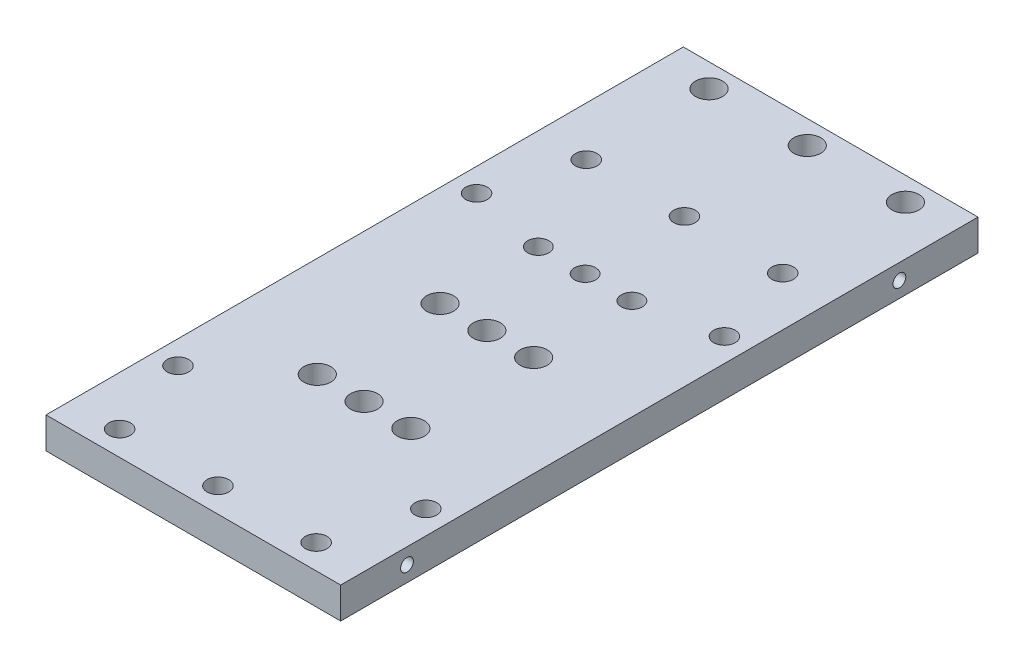
SolidWorks part; units mm, degrees
material "6061 Alloy"
ref_plane "Front Plane" through (0, 0, 0) normal (0, 0, 1) x (1, 0, 0)
ref_plane "Top Plane" through (0, 0, 0) normal (0, 1, 0) x (1, 0, 0)
ref_plane "Right Plane" through (0, 0, 0) normal (1, 0, 0) x (0, 0, -1)
sketch "Sketch1" plane through (0, 0, 0) normal (0, 1, 0) x (1, 0, 0)
  line L1 (-30, 80) -> (30, 80)
  line L2 (-30, 80) -> (-30, -80)
  line L3 (-30, -80) -> (30, -80)
  line L4 (30, 80) -> (30, -80)
  line L5 (0, -80) -> (0, 80) construction
  line L6 (-30, 0) -> (30, 0) construction
  point P0 (0, 0)
  dimension "D1" = 60
  dimension "D2" = 160
extrude "Boss-Extrude1" add sketch "Sketch1" along normal mid plane 6.35
sketch "Sketch3" plane through (0, 0, 0) normal (0, 1, 0) x (1, 0, 0)
  line L0 (0, 75.2375) -> (20, 75.2375) construction
  line L5 (0, -80) -> (0, 80) construction
  line L6 (-30, 0) -> (30, 0) construction
  line L7 (0, 50.2375) -> (20, 50.2375) construction
  line L8 (30, 80) -> (-30, 80) construction
  line L9 (-30, 80) -> (-30, -80) construction
  line L10 (-30, -80) -> (30, -80) construction
  line L11 (30, -80) -> (30, 80) construction
  line L12 (0, -44.7625) -> (20, -44.7625) construction
  circle A0 centre (20, 75.2375) radius 2.75
  circle A1 centre (20, 50.2375) radius 2.2
  circle A2 centre (-20, 50.2375) radius 2.2
  circle A3 centre (-20, 75.2375) radius 2.75
  circle A4 centre (0, 75.2375) radius 2.75
  circle A5 centre (0, 50.2375) radius 2.2
  circle A6 centre (20, -44.7625) radius 2.2
  circle A7 centre (-20, -44.7625) radius 2.2
  circle A8 centre (0, -44.7625) radius 2.2
  point P0 (0, 0)
  dimension "D4" = 5.5
  dimension "D5" = 4.4
  dimension "D1" = 4.7625
  dimension "D2" = 25
  dimension "D3" = 20
  dimension "D6" = 2
extrude "M4/5_through" cut sketch "Sketch3" against normal up to surface (3.175 mm away) and the other way blind 6.35 up to face at (0, -3.175, 0)
sketch "Sketch4" plane through (0, 0, -80) normal (0, 0, -1) x (-1, 0, 0)
  line L0 (0, 0) -> (-12, 0) construction
  line L1 (0, 0) -> (0, 3.175) construction
  line L2 (-30, 3.175) -> (30, 3.175) construction
  circle A0 centre (-12, 0) radius 1.3
  circle A1 centre (12, 0) radius 1.3
  dimension "D1" = 2.6
  dimension "D2" = 12
extrude "M3_DRILL" cut sketch "Sketch4" against normal blind 8
sketch "Sketch5" plane through (0, 3.175, 0) normal (0, 1, 0) x (1, 0, 0)
  line L0 (-20, -44.7625) -> (0, -44.7625) construction
  line L1 (-30, 80) -> (-30, -80) construction
  line L2 (0, 0) -> (0, -23.6676) construction
  line L3 (-20, 50.2375) -> (-20, -44.7625) construction
  line L4 (-20, 2.7375) -> (-9.1233, 2.7375) construction
  circle A0 centre (-25.2375, -27.6625) radius 2.2
  circle A1 centre (25.2375, -27.6625) radius 2.2
  circle A2 centre (25.2375, 33.1375) radius 2.2
  circle A3 centre (-25.2375, 33.1375) radius 2.2
  dimension "D2" = 4.4
  dimension "D1" = 17.1
  dimension "D3" = 4.7625
extrude "M4_through" cut sketch "Sketch5" against normal up to surface (6.35 mm away) up to face at (20, -3.175, -48.0375)
sketch "Sketch6" plane through (0, 3.175, 0) normal (0, 1, 0) x (1, 0, 0)
  line L0 (0, 0) -> (0, -64.4319) construction
  circle A0 centre (0, 30) radius 2.15
  circle A1 centre (9.53, 30) radius 2.15
  circle A2 centre (-9.53, 30) radius 2.15
  dimension "D1" = 4.3
  dimension "D4" = 30
  dimension "D2" = 2
  dimension "D3" = 2
extrude "M5_DRILL" cut sketch "Sketch6" against normal up to surface (6.35 mm away) up to face at (-25.2375, -3.175, -30.9375)
sketch "Sketch7" plane through (0, 3.175, 0) normal (0, 1, 0) x (1, 0, 0)
  line L0 (0, 30) -> (0, -15) construction
  circle A0 centre (0, 10) radius 2.75
  circle A1 centre (0, -15) radius 2.75
  circle A2 centre (9.53, 10) radius 2.75
  circle A3 centre (9.53, -15) radius 2.75
  circle A4 centre (-9.53, 10) radius 2.75
  circle A5 centre (-9.53, -15) radius 2.75
  dimension "D3" = 5.5
  dimension "D1" = 45
  dimension "D2" = 20
  dimension "D4" = 2
  dimension "D5" = 2
extrude "M5_through" cut sketch "Sketch7" against normal up to surface (6.35 mm away) up to face at (-9.53, -3.175, -27.85)
sketch "Sketch8" plane through (0, 3.175, 0) normal (0, 1, 0) x (1, 0, 0)
  line L0 (-20, -44.7625) -> (20, -44.7625) construction
  line L1 (30, -80) -> (30, 80) construction
  line L2 (-30, -80) -> (30, -80)
  line L3 (-30, -80) -> (-30, -49.7625)
  line L4 (-30, -49.7625) -> (30, -49.7625)
  line L5 (30, -80) -> (30, -49.7625)
  line L6 (0, -49.7625) -> (0, -80) construction
  line L7 (-30, -64.8812) -> (30, -64.8812) construction
  point P260 (0, -64.8812)
  dimension "D1" = 5
extrude "Cut-Extrude3" cut sketch "Sketch8" against normal up to surface (6.35 mm away) up to face at (-9.53, -3.175, -7.25)
sketch "Sketch9" plane through (-30, 0, 0) normal (-1, 0, 0) x (0, 0, 1)
  line L0 (-80, 0) -> (49.7625, 0) construction
  line L1 (-80, 3.175) -> (-80, -3.175) construction
  line L2 (49.7625, -3.175) -> (49.7625, 3.175) construction
  line L3 (36.2625, 0) -> (36.2625, 96.35) construction
  line L4 (-64, 0) -> (-64, 96.35) construction
  circle A0 centre (-64, 0) radius 1.3
  circle A1 centre (36.2625, 0) radius 1.3
  circle A2 centre (36.2625, 96.35) radius 1.3 construction
  dimension "D1" = 2.6
  dimension "D2" = 2.6
extrude "Cut-Extrude4" cut sketch "Sketch9" against normal blind 10
mirror "Mirror1" about plane through (0, 0, 0) normal (1, 0, 0) of "Cut-Extrude4"
